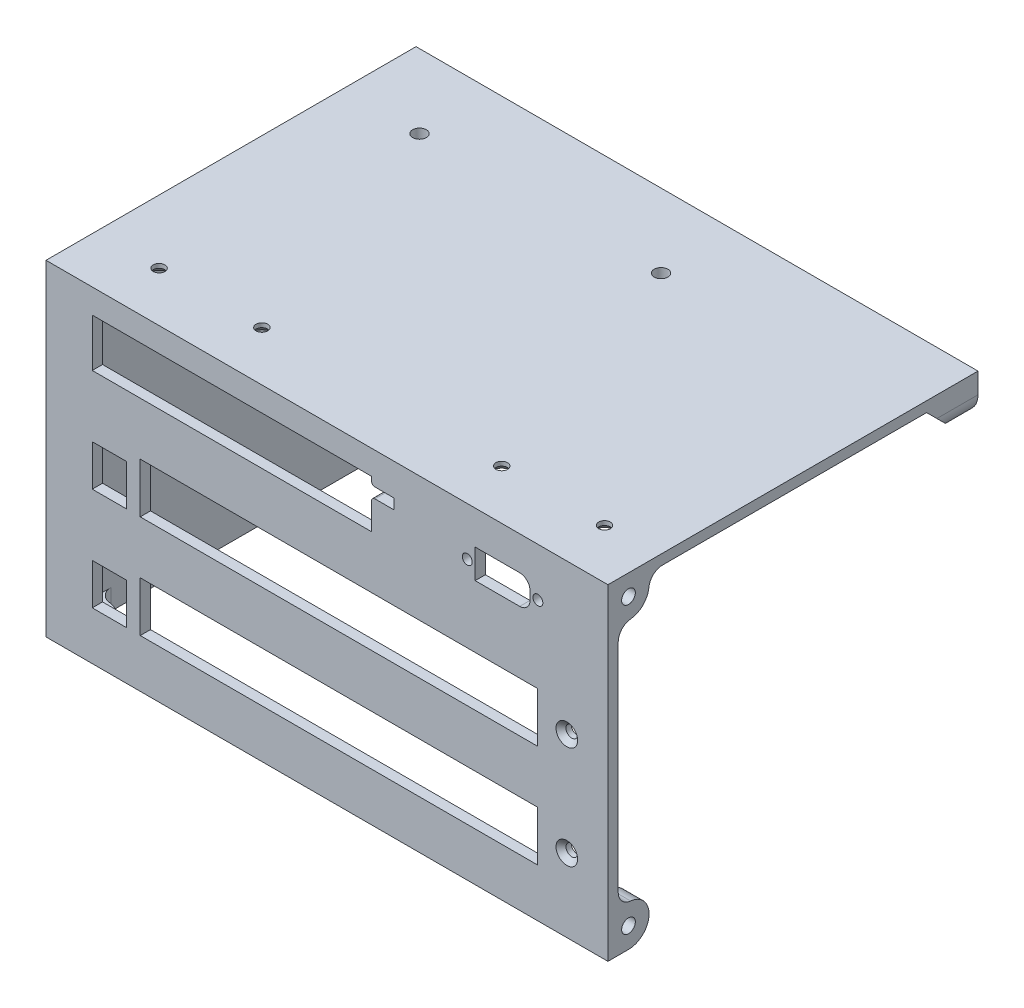
SolidWorks part; units mm, degrees
ref_plane "Front Plane" through (0, 0, 0) normal (0, 0, 1) x (1, 0, 0)
ref_plane "Top Plane" through (0, 0, 0) normal (0, 1, 0) x (1, 0, 0)
ref_plane "Right Plane" through (0, 0, 0) normal (1, 0, 0) x (0, 0, -1)
sketch "Sketch1" plane through (0, 0, 0) normal (0, 0, 1) x (1, 0, 0)
  line L0 (109.9806, -22.9) -> (-6.0194, -22.9)
  line L1 (130.4806, -37) -> (-30.5194, -37)
  line L2 (130.4806, -37) -> (130.4806, 55.2)
  line L3 (130.4806, 55.2) -> (-30.5194, 55.2)
  line L4 (-30.5194, -37) -> (-30.5194, 55.2)
  line L5 (109.4806, -22.4) -> (-5.5194, -22.4) construction
  line L6 (109.4806, -22.4) -> (109.4806, -8.8) construction
  line L7 (109.4806, -8.8) -> (-5.5194, -8.8) construction
  line L8 (-5.5194, -22.4) -> (-5.5194, -8.8) construction
  line L9 (109.4806, 7.6) -> (-5.5194, 7.6) construction
  line L10 (109.4806, 7.6) -> (109.4806, 21.2) construction
  line L11 (109.4806, 21.2) -> (-5.5194, 21.2) construction
  line L12 (-5.5194, 7.6) -> (-5.5194, 21.2) construction
  line L13 (-6.0194, -22.9) -> (-6.0194, -8.3)
  line L14 (109.9806, -8.3) -> (-6.0194, -8.3)
  line L15 (109.9806, -22.9) -> (109.9806, -8.3)
  line L16 (109.9806, 7.1) -> (-6.0194, 7.1)
  line L17 (-6.0194, 7.1) -> (-6.0194, 21.7)
  line L18 (109.9806, 21.7) -> (-6.0194, 21.7)
  line L19 (109.9806, 7.1) -> (109.9806, 21.7)
  line L20 (-30.5194, -27) -> (-30.5194, -13.1847) construction
  line L21 (-30.5194, -30) -> (123.4806, -30) construction
  line L22 (61.4806, 51.1) -> (-20.0194, 51.1)
  line L23 (-20.0194, 51.1) -> (-20.0194, 37.1)
  line L24 (-20.0194, 37.1) -> (61.4806, 37.1)
  line L25 (61.4806, 37.1) -> (61.4806, 45.9)
  line L26 (60.9806, 50.6) -> (-19.5194, 50.6)
  line L27 (-19.5194, 50.6) -> (-19.5194, 37.6)
  line L28 (-19.5194, 37.6) -> (60.9806, 37.6)
  line L29 (60.9806, 37.6) -> (60.9806, 50.6)
  line L30 (60.9806, 50.6) -> (-19.5194, 50.6) construction
  line L31 (-19.5194, 50.6) -> (-19.5194, 37.6) construction
  line L32 (-19.5194, 37.6) -> (60.9806, 37.6) construction
  line L33 (60.9806, 37.6) -> (60.9806, 50.6) construction
  line L34 (104.7306, 48.35) -> (91.7306, 48.35)
  line L35 (91.7306, 48.35) -> (91.7306, 39.85)
  line L36 (91.7306, 39.85) -> (104.7306, 39.85)
  line L37 (107.7306, 42.85) -> (107.7306, 45.35)
  line L38 (68.9806, 52.2) -> (-20.5194, 52.2) construction
  line L39 (104.7306, 48.15) -> (91.9306, 48.15)
  line L40 (91.9306, 48.15) -> (91.9306, 40.05)
  line L41 (91.9306, 40.05) -> (104.7306, 40.05)
  line L42 (107.5306, 42.85) -> (107.5306, 45.35)
  line L43 (104.7306, 48.15) -> (91.9306, 48.15) construction
  line L44 (91.9306, 48.15) -> (91.9306, 40.05) construction
  line L45 (91.9306, 40.05) -> (104.7306, 40.05) construction
  line L46 (107.5306, 42.85) -> (107.5306, 45.35) construction
  line L67 (-19.5194, -22.4) -> (-10.5194, -22.4) construction
  line L68 (-10.5194, -22.4) -> (-10.5194, -11.4) construction
  line L69 (-10.5194, -11.4) -> (-19.5194, -11.4) construction
  line L70 (-19.5194, -11.4) -> (-19.5194, -22.4) construction
  line L71 (-19.5194, 7.6) -> (-10.5194, 7.6) construction
  line L72 (-10.5194, 7.6) -> (-10.5194, 18.6) construction
  line L73 (-10.5194, 18.6) -> (-19.5194, 18.6) construction
  line L74 (-19.5194, 18.6) -> (-19.5194, 7.6) construction
  line L75 (-19.5194, -22.4) -> (-10.5194, -22.4) construction
  line L76 (-10.5194, -22.4) -> (-10.5194, -11.4) construction
  line L77 (-10.5194, -11.4) -> (-19.5194, -11.4) construction
  line L78 (-19.5194, -11.4) -> (-19.5194, -22.4) construction
  line L79 (-19.5194, 7.6) -> (-10.5194, 7.6) construction
  line L80 (-10.5194, 7.6) -> (-10.5194, 18.6) construction
  line L81 (-10.5194, 18.6) -> (-19.5194, 18.6) construction
  line L82 (-19.5194, 18.6) -> (-19.5194, 7.6) construction
  line L83 (-20.0194, -22.9) -> (-10.0194, -22.9)
  line L84 (-10.0194, -22.9) -> (-10.0194, -10.9)
  line L85 (-10.0194, -10.9) -> (-20.0194, -10.9)
  line L86 (-20.0194, -10.9) -> (-20.0194, -22.9)
  line L87 (-20.0194, 7.1) -> (-10.0194, 7.1)
  line L88 (-10.0194, 7.1) -> (-10.0194, 19.1)
  line L89 (-10.0194, 19.1) -> (-20.0194, 19.1)
  line L90 (-20.0194, 19.1) -> (-20.0194, 7.1)
  line L95 (68.0806, 45.9) -> (68.0806, 48.9)
  line L96 (68.0806, 48.9) -> (61.4806, 48.9)
  line L98 (61.4806, 45.9) -> (68.0806, 45.9)
  line L99 (67.5806, 46.4) -> (67.5806, 48.4)
  line L100 (67.5806, 48.4) -> (63.5806, 48.4)
  line L101 (63.5806, 48.4) -> (63.5806, 46.4)
  line L102 (63.5806, 46.4) -> (67.5806, 46.4)
  line L103 (67.5806, 46.4) -> (67.5806, 48.4) construction
  line L104 (67.5806, 48.4) -> (63.5806, 48.4) construction
  line L105 (63.5806, 48.4) -> (63.5806, 46.4) construction
  line L106 (63.5806, 46.4) -> (67.5806, 46.4) construction
  line L107 (68.0806, 48.9) -> (63.0806, 48.9) construction
  line L108 (63.0806, 45.9) -> (68.0806, 45.9) construction
  line L109 (63.0806, 48.9) -> (63.0806, 45.9) construction
  line L110 (61.4806, 48.9) -> (61.4806, 51.1)
  line L111 (61.4806, 37.1) -> (61.4806, 51.1) construction
  arc A0 (104.7306, 39.85) -> (107.7306, 42.85) centre (104.7306, 42.85) ccw
  arc A1 (107.7306, 45.35) -> (104.7306, 48.35) centre (104.7306, 45.35) ccw
  arc A2 (104.7306, 40.05) -> (107.5306, 42.85) centre (104.7306, 42.85) ccw
  arc A3 (107.5306, 45.35) -> (104.7306, 48.15) centre (104.7306, 45.35) ccw
  arc A4 (104.7306, 40.05) -> (107.5306, 42.85) centre (104.7306, 42.85) ccw construction
  arc A5 (107.5306, 45.35) -> (104.7306, 48.15) centre (104.7306, 45.35) ccw construction
  dimension "D3" = 7
  dimension "D4" = 7
  dimension "D5" = 3
  dimension "D11" = 0
  dimension "D1" = 0.5
  dimension "D2" = 0.5
  dimension "D6" = 0
  dimension "D7" = 0.5
  dimension "D8" = 0.5
  dimension "D9" = 0
  dimension "D10" = 0.5
  dimension "D12" = 0.2
extrude "Boss-Extrude1" add sketch "Sketch1" along normal blind 3
sketch "Sketch2" plane through (0, 0, 3) normal (0, 0, 1) x (1, 0, 0)
  point P1 (118.4806, 14.4)
  point P3 (118.4806, -15.6)
sketch "Sketch4" plane through (-30.5194, 0, 0) normal (-1, 0, 0) x (0, 0, 1)
  line L1 (3, 55.2) -> (-105, 55.2)
  line L2 (3, 55.2) -> (3, -37)
  line L3 (3, -37) -> (-105, -37)
  line L4 (-105, 55.2) -> (-105, -37)
  dimension "D1" = 3
extrude "Boss-Extrude2" add sketch "Sketch4" along normal blind 3
sketch "Sketch5" plane through (0, 55.2, 0) normal (0, 1, 0) x (1, 0, 0)
  line L0 (-33.5194, -3) -> (-33.5194, 105) construction
  line L1 (130.4806, -3) -> (-33.5194, -3)
  line L2 (130.4806, -3) -> (130.4806, 105)
  line L3 (130.4806, 105) -> (-33.5194, 105)
  line L4 (-33.5194, -3) -> (-33.5194, 105)
extrude "Boss-Extrude3" add sketch "Sketch5" along normal blind 3
sketch "Sketch6" plane through (-33.5194, 0, 0) normal (-1, 0, 0) x (0, 0, 1)
  point P0 (-90, 14.4)
  point P1 (-90, -15.6)
  point P5 (-12, 14.4)
  point P8 (-12, -15.6)
hole_wizard "CSK for M3 Flat Head Machine Screw1" positions "Sketch2" profile "Sketch3" countersink size "M3" standard "ANSI Metric" end condition up to next
sketch "Sketch3" plane through (118.4806, 14.4, 3) normal (1, 0, 0) x (0, -1, 0)
  line L0 (0, 0) -> (0, 3)
  line L1 (0, 3) -> (1.7, 3)
  line L2 (1.7, 3) -> (1.7, 1.45)
  line L3 (1.7, 1.45) -> (3.15, 0)
  line L5 (3.15, 0) -> (0, 0)
  line L6 (-1.7, 1.45) -> (-3.15, 0) construction
  line L11 (0, -6.35) -> (0, 107.95) construction
  dimension "Thru Hole Dia." = 3.4
  dimension "Thru Hole Depth" = 3
  dimension "Near C'Sink Dia." = 6.3
  dimension "Near C'Sink Angle" = 90
hole_wizard "CSK for M3 Flat Head Machine Screw2" positions "Sketch6" profile "Sketch7" countersink size "M3" standard "ANSI Metric" end condition up to next
sketch "Sketch7" plane through (-33.5194, 14.4, -90) normal (0, 1, 0) x (0, 0, 1)
  line L0 (0, 0) -> (0, 3)
  line L1 (0, 3) -> (1.7, 3)
  line L2 (1.7, 3) -> (1.7, 1.45)
  line L3 (1.7, 1.45) -> (3.15, 0)
  line L5 (3.15, 0) -> (0, 0)
  line L6 (-1.7, 1.45) -> (-3.15, 0) construction
  line L11 (0, -6.35) -> (0, 107.95) construction
  dimension "Thru Hole Dia." = 3.4
  dimension "Thru Hole Depth" = 3
  dimension "Near C'Sink Dia." = 6.3
  dimension "Near C'Sink Angle" = 90
sketch "Sketch8" plane through (0, -37, 0) normal (0, -1, 0) x (1, 0, 0)
  line L2 (-33.5194, -105) -> (-33.5194, 3) construction
  line L8 (-33.5194, -105) -> (-30.5194, -105) construction
  line L9 (-27.5194, -105) -> (-33.5194, -105)
  line L10 (-33.5194, -105) -> (-33.5194, -99)
  circle A1 centre (-27.5194, -3) radius 2
  circle A2 centre (-27.5194, -3) radius 6
  circle A3 centre (-27.5194, -99) radius 2
  arc A5 (-27.5194, -105) -> (-33.5194, -99) centre (-27.5194, -99) ccw
  dimension "D3" = 6
  dimension "D1" = 4
  dimension "D4" = 4
  dimension "D2" = 6
  dimension "D5" = 6
  dimension "D6" = 6
extrude "Boss-Extrude5" add sketch "Sketch8" against normal blind 6
fillet "Fillet2" radius 4 2 edges at (-30.5194, -34, -8.1962) (-22.3233, -34, 0)
sketch "Sketch10" plane through (130.4806, 0, 0) normal (1, 0, 0) x (0, 0, -1)
  line L0 (-3, 58.2) -> (105, 58.2) construction
  line L1 (-3, -37) -> (-3, 58.2) construction
  line L2 (-3, -37) -> (0, -37) construction
  line L3 (-3, -31) -> (-3, -37)
  line L4 (-3, -37) -> (3, -37)
  circle A0 centre (3, 52.2) radius 2
  circle A1 centre (3, 52.2) radius 6
  circle A2 centre (3, -31) radius 2
  arc A3 (3, -37) -> (-3, -31) centre (3, -31) ccw
  dimension "D1" = 4
  dimension "D4" = 4
  dimension "D2" = 6
  dimension "D3" = 6
  dimension "D6" = 6
extrude "Boss-Extrude6" add sketch "Sketch10" against normal blind 6
fillet "Fillet3" radius 4 3 edges at (127.4806, 55.2, -8.1962) (127.4806, 47.0038, 0) (127.4806, -25.8038, 0)
sketch "Sketch11" plane through (0, 0, -105) normal (0, 0, -1) x (-1, 0, 0)
  line L0 (33.5194, 58.2) -> (33.5194, -37) construction
  line L1 (-130.4806, 58.2) -> (33.5194, 58.2) construction
  line L2 (-130.4806, 58.2) -> (-130.4806, 55.2) construction
  line L3 (-124.4806, 58.2) -> (-130.4806, 58.2)
  line L4 (-130.4806, 58.2) -> (-130.4806, 52.2)
  circle A0 centre (27.5194, 52.2) radius 2
  circle A1 centre (27.5194, 52.2) radius 6
  circle A2 centre (-124.4806, 52.2) radius 2
  arc A3 (-130.4806, 52.2) -> (-124.4806, 58.2) centre (-124.4806, 52.2) ccw
  dimension "D1" = 4
  dimension "D4" = 4
  dimension "D2" = 6
  dimension "D3" = 6
  dimension "D5" = 6
  dimension "D6" = 6
extrude "Boss-Extrude7" add sketch "Sketch11" against normal blind 6
fillet "Fillet4" radius 4 3 edges at (-30.5194, 47.0038, -102) (-22.3233, 55.2, -102) (119.2844, 55.2, -102)
chamfer "Chamfer1" distance 9 angle 45 2 edges at (122.5057, 55.2, -99) (-24.0445, 55.2, -99)
chamfer "Chamfer2" distance 20 angle 65 1 edges at (-30.5194, -34, -93.8038) first distance on face at (-30.5194, 3.9182, -64.6825)
sketch "Sketch12" plane through (0, 55.2, 0) normal (0, -1, 0) x (1, 0, 0)
  point P0 (-11.0194, -83.5)
  point P1 (59.4806, -83.5)
hole_wizard "Ø4.0mm Dowel Hole1" positions "Sketch12" profile "Sketch13" hole size "Ø4.0" standard "DIN" end condition up to next
sketch "Sketch13" plane through (-11.0194, 55.2, -83.5) normal (1, 0, 0) x (0, 0, -1)
  line L0 (0, 0) -> (0, 3)
  line L1 (0, 3) -> (2, 3)
  line L2 (2, 3) -> (2, 0)
  line L5 (2, 0) -> (0, 0)
  line L11 (0, -6.35) -> (0, 107.95) construction
  dimension "Thru Hole Dia." = 4
  dimension "Thru Hole Depth" = 3
sketch "Sketch14" plane through (0, 55.2, 0) normal (0, -1, 0) x (1, 0, 0)
  circle A0 centre (-11.0194, -83.5) radius 4
  circle A1 centre (59.4806, -83.5) radius 4
  circle A2 centre (59.4806, -83.5) radius 2 construction
  circle A3 centre (-11.0194, -83.5) radius 2 construction
  circle A4 centre (59.4806, -83.5) radius 2
  circle A5 centre (-11.0194, -83.5) radius 2
  circle A6 centre (80.2306, -81.5) radius 2
  circle A7 centre (80.2306, -81.5) radius 4
  circle A8 centre (80.2306, -81.5) radius 1.6 construction
  circle A9 centre (119.2306, -81.5) radius 2
  circle A10 centre (119.2306, -81.5) radius 4
  circle A11 centre (80.2306, -28.5) radius 2
  circle A12 centre (80.2306, -28.5) radius 4
  circle A13 centre (119.2306, -28.5) radius 2
  circle A14 centre (119.2306, -28.5) radius 4
  dimension "D1" = 8
  dimension "D2" = 4
  dimension "D3" = 8
extrude "Boss-Extrude8" add sketch "Sketch14" along normal blind 3
chamfer "Chamfer3" distance 3 angle 45 6 edges at (55.4806, 55.2, -83.5) (-15.0194, 55.2, -83.5) (76.2306, 55.2, -28.5) (115.2306, 55.2, -28.5) (115.2306, 55.2, -81.5) (76.2306, 55.2, -81.5)
fillet "Fillet5" radius 1 2 edges at (61.4806, 48.9, 1.5) (61.4806, 45.9, 1.5)
sketch "Sketch19" plane through (0, 0, 3) normal (0, 0, 1) x (1, 0, 0)
  point P18 (89.4306, 44.1)
  point P21 (110.0306, 44.1)
hole_wizard "M2.5 Clearance Hole1" positions "Sketch19" profile "Sketch18" hole size "M2.5" standard "DIN"
sketch "Sketch18" plane through (89.4306, 44.1, 3) normal (1, 0, 0) x (0, -1, 0)
  line L0 (0, 0) -> (0, 5.8712)
  line L1 (0, 5.8712) -> (1.45, 5)
  line L2 (1.45, 5) -> (1.45, 0)
  line L5 (1.45, 0) -> (0, 0)
  line L10 (0, 5.8712) -> (-1.45, 5) construction
  line L11 (0, -6.35) -> (0, 107.95) construction
  dimension "Hole Dia." = 2.9
  dimension "Hole Depth" = 5
  dimension "Drill Angle" = 118
sketch "Sketch20" plane through (0, 55.2, 0) normal (0, -1, 0) x (1, 0, 0)
  point P0 (114.9806, -11.5)
  point P1 (84.9806, -11.5)
  point P3 (14.9806, -11.5)
  point P5 (-15.0194, -11.5)
hole_wizard "CSK for M3 socket countersunk head screw1" positions "Sketch20" profile "Sketch21" countersink size "M3" standard "DIN" end condition through all
sketch "Sketch21" plane through (114.9806, 55.2, -11.5) normal (1, 0, 0) x (0, 0, -1)
  line L0 (0, 0) -> (0, 3)
  line L1 (0, 3) -> (1.7, 3)
  line L2 (1.7, 3) -> (1.7, 1.77)
  line L3 (1.7, 1.77) -> (3.47, 0)
  line L5 (3.47, 0) -> (0, 0)
  line L6 (-1.7, 1.77) -> (-3.47, 0) construction
  line L11 (0, -6.35) -> (0, 107.95) construction
  dimension "Thru Hole Dia." = 3.4
  dimension "Thru Hole Depth" = 3
  dimension "Near C'Sink Dia." = 6.94
  dimension "Near C'Sink Angle" = 90
chamfer "Chamfer4" distance 2 angle 45 3 edges at (-30.5194, 12.1, 0) (-30.5194, 55.2, -45) (46.9806, 55.2, 0)
